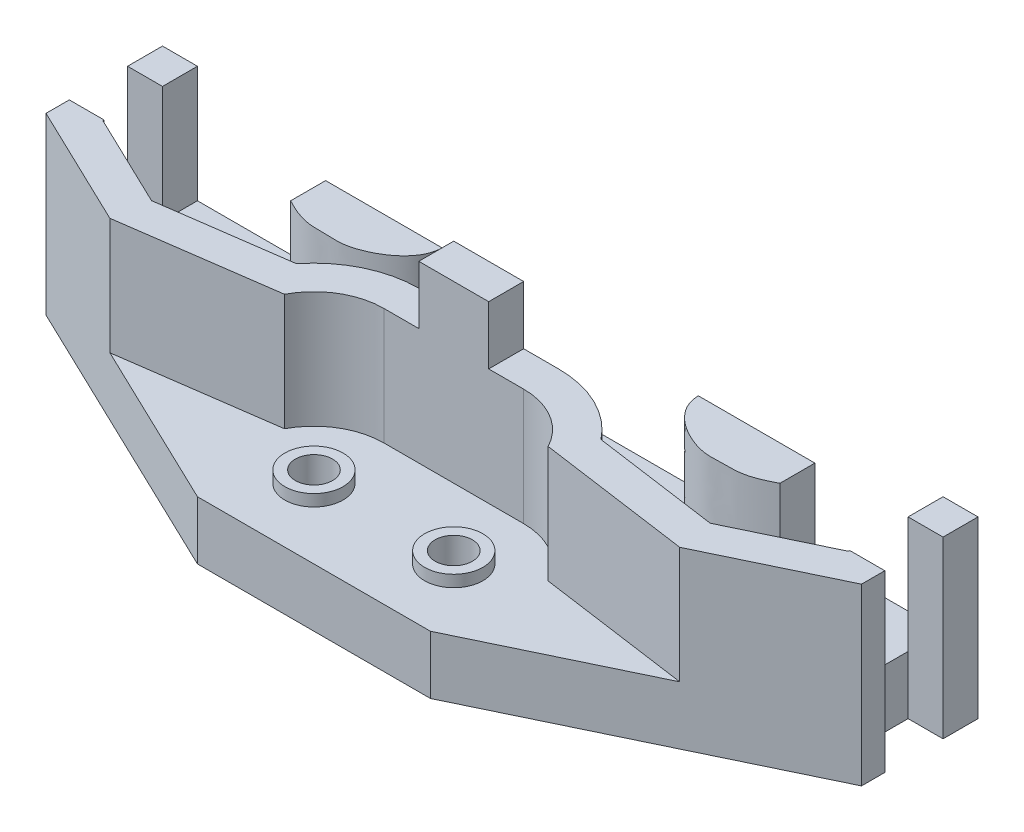
SolidWorks part; units mm, degrees
ref_plane "Front Plane" through (0, 0, 0) normal (0, 0, 1) x (1, 0, 0)
ref_plane "Top Plane" through (0, 0, 0) normal (0, 1, 0) x (1, 0, 0)
ref_plane "Right Plane" through (0, 0, 0) normal (1, 0, 0) x (0, 0, -1)
sketch "Sketch1" plane through (0, 0, 0) normal (0, 1, 0) x (1, 0, 0)
  line L0 (0, 0) -> (20, 0)
  line L1 (10, 0) -> (10, 12) construction
  line L2 (10, 12) -> (-25, 12) construction
  line L3 (0, 0) -> (-25, 12)
  line L4 (-25, 12) -> (-25, 22)
  line L5 (-25, 22) -> (45, 22)
  line L6 (45, 22) -> (45, 12)
  line L7 (45, 12) -> (20, 0)
  dimension "D1" = 35
  dimension "D2" = 20
  dimension "D3" = 12
  dimension "D4" = 70
  dimension "D5" = 10
  dimension "D6" = 10
extrude "Boss-Extrude1" add sketch "Sketch1" along normal blind 5
ref_plane "Plane1" through (10, 0, 0) normal (1, 0, 0) x (0, 0, -1)
sketch "Sketch2" plane through (0, 5, 0) normal (0, 1, 0) x (1, 0, 0)
  line L0 (10, 0) -> (10, 22) construction
  line L1 (0, 0) -> (20, 0) construction
  line L2 (45, 22) -> (-25, 22) construction
  circle A0 centre (4, 6) radius 1.6
  circle A1 centre (16, 6) radius 1.6
  dimension "D1" = 3.2
  dimension "D2" = 6
  dimension "D3" = 6
extrude "Cut-Extrude1" cut sketch "Sketch2" against normal blind 3
sketch "Sketch3" plane through (0, 5, 0) normal (0, 1, 0) x (1, 0, 0)
  line L0 (4, 6) -> (-8.7631, 4.2063) construction
  line L1 (-25, 12) -> (0, 0) construction
  line L2 (-8.7631, 4.2063) -> (-8.7631, 22) construction
  line L3 (45, 22) -> (-25, 22) construction
  line L4 (-2.3815, 5.1031) -> (-2.8686, 8.5691) construction
  line L5 (-2.8686, 8.5691) -> (4.0027, 9.5348) construction
  line L6 (-1.3131, 8.7877) -> (-14.4587, 6.9402)
  line L7 (10, 0) -> (10, 22) construction
  line L8 (0, 0) -> (20, 0) construction
  line L10 (-14.4587, 6.9402) -> (-25, 12)
  line L11 (-25, 12) -> (-25, 22)
  line L12 (-25, 22) -> (-22, 22)
  line L13 (-21.9703, 13.8734) -> (-25, 15.3277) construction
  line L14 (-21.9703, 13.8734) -> (-9.0961, 7.6939) construction
  line L15 (-19.7294, 9.4701) -> (-13.715, 22) construction
  line L17 (-3.069, 11.5704) -> (-13.9782, 10.0372)
  line L19 (-7.8859, 7.8639) -> (-9.8726, 22) construction
  line L21 (4, 12) -> (4, 15) construction
  line L30 (-22, 22) -> (-22, 13.8877)
  line L32 (0.4296, 9.0326) -> (0.012, 12.0034) construction
  line L33 (0.012, 12.0034) -> (-19.3407, 9.2836) construction
  line L34 (-22, 13.8877) -> (-13.9782, 10.0372)
  line L35 (4, 15) -> (16, 15)
  line L36 (4, 12) -> (16, 12)
  line L37 (21.3131, 8.7877) -> (34.4587, 6.9402)
  line L38 (34.4587, 6.9402) -> (45, 12)
  line L39 (45, 12) -> (45, 22)
  line L40 (45, 22) -> (42, 22)
  line L41 (42, 22) -> (42, 13.8877)
  line L42 (42, 13.8877) -> (33.9782, 10.0372)
  line L43 (23.069, 11.5704) -> (33.9782, 10.0372)
  arc A0 (-1.3131, 8.7877) -> (4, 12) centre (4, 6) cw
  arc A4 (4, 15) -> (-3.069, 11.5704) centre (4, 6) ccw
  arc A5 (21.3131, 8.7877) -> (16, 12) centre (16, 6) ccw
  arc A6 (16, 15) -> (23.069, 11.5704) centre (16, 6) cw
  point P34 (10, 12)
  point P35 (10, 12)
  point P36 (10, 15)
  point P52 (10, 15)
  dimension "D4" = 6
  dimension "D1" = 82
  dimension "D2" = 3.5
  dimension "D3" = 90
  dimension "D5" = 90
  dimension "D6" = 90
  dimension "D7" = 3
  dimension "D8" = 3
  dimension "D9" = 3
  dimension "D10" = 3
  dimension "D11" = 3
  dimension "D12" = 90
extrude "Boss-Extrude2" add sketch "Sketch3" along normal blind 10
sketch "Sketch9" plane through (0, 15, 0) normal (0, 1, 0) x (1, 0, 0)
  line L0 (10, 12) -> (10, 15) construction
  line L1 (4, 12) -> (16, 12) construction
  line L2 (16, 15) -> (4, 15) construction
  line L3 (16, 15) -> (4, 15) construction
  line L4 (7, 12) -> (13, 12)
  line L5 (7, 12) -> (7, 15)
  line L6 (7, 15) -> (13, 15)
  line L7 (13, 12) -> (13, 15)
  dimension "D1" = 3
  dimension "D2" = 3
extrude "Boss-Extrude3" add sketch "Sketch9" along normal blind 5
sketch "Sketch12" plane through (0, 15, 0) normal (0, 1, 0) x (1, 0, 0)
  line L0 (-25, 22) -> (-25, 12) construction
  line L1 (-25, 19) -> (-22, 19)
  line L2 (-25, 19) -> (-25, 14)
  line L3 (-25, 14) -> (-22, 14)
  line L4 (-22, 19) -> (-22, 14)
  line L5 (-22, 13.8877) -> (-22, 22) construction
  line L6 (-22, 22) -> (-25, 22) construction
  line L7 (10, 22) -> (10, 0) construction
  line L8 (42, 22) -> (-22, 22) construction
  line L9 (0, 0) -> (20, 0) construction
  line L10 (45, 14) -> (42, 14)
  line L11 (42, 19) -> (42, 14)
  line L12 (45, 19) -> (42, 19)
  line L13 (45, 19) -> (45, 14)
  dimension "D1" = 3
  dimension "D2" = 5
extrude "Cut-Extrude4" cut sketch "Sketch12" against normal blind 17
sketch "Sketch14" plane through (0, 5, 0) normal (0, 1, 0) x (1, 0, 0)
  line L0 (42, 22) -> (-22, 22) construction
  line L1 (21, 22) -> (31, 22)
  line L3 (26, 18) -> (28.2891, 18)
  line L4 (31, 22) -> (31, 19)
  line L5 (10, 22) -> (10, 0) construction
  line L6 (0, 0) -> (20, 0) construction
  line L7 (-0.7999, 18) -> (-10.7999, 18)
  line L8 (-11, 22) -> (-10.7999, 18)
  line L9 (-1, 22) -> (-11, 22)
  line L10 (-1, 22) -> (-0.7999, 18)
  line L13 (25.9305, 18) -> (23.1394, 18) construction
  line L14 (21, 19.713) -> (21, 24.3845) construction
  spline S0 degree 3 poles (21, 22) (21, 19.7457) (24.6092, 17.8685) (27.9309, 18.1418) (28.7395, 17.7851) (31, 19) knots 0 0 0 0 0.402282 0.502282 1 1 1 1
  point P2 (31.102, 19)
  point P15 (21.2001, 22)
  point P18 (0, 0)
  point P24 (26.0428, 18)
  line M17 (42, 22) -> (-22, 22)
  dimension "D1" = 4
  dimension "D2" = 10
  dimension "D3" = 3
  dimension "D4" = 21
  dimension "D5" = 5
extrude "Boss-Extrude5" add sketch "Sketch14" along normal offset from surface (7 mm away) 3 contours S0 L4 M17 region at (26.4101, 5, -20.2182) up to face at (28.8051, 15, -12.2313)
sketch "Sketch20" plane through (0, 5, 0) normal (0, 1, 0) x (1, 0, 0)
  line L0 (10, 0) -> (10, 12) construction
  line L1 (0, 0) -> (20, 0) construction
  line L2 (7, 12) -> (13, 12) construction
  circle A0 centre (4, 6) radius 2.5
  circle A1 centre (4, 6) radius 1.6
  circle A2 centre (16, 6) radius 2.5
  circle A3 centre (16, 6) radius 1.6
  dimension "D1" = 5
extrude "Boss-Extrude7" add sketch "Sketch20" along normal blind 1
sketch "Sketch21" plane through (0, 0, 0) normal (0, -1, 0) x (1, 0, 0)
  line L0 (45, -22) -> (-25, -22) construction
  line L1 (16, -22) -> (4, -22)
  line L2 (16, -22) -> (16, -12)
  line L3 (16, -12) -> (4, -12)
  line L4 (4, -22) -> (4, -12)
  point P9 (10, -22)
  point P10 (10, -22)
  dimension "D1" = 12
  dimension "D2" = 10
extrude "Boss-Extrude9" add sketch "Sketch21" along normal blind 8
sketch "Sketch25" plane through (16, 0, 0) normal (1, 0, 0) x (0, 0, -1)
  line L0 (22, -8) -> (12, -8) construction
  line L1 (10.942, 0) -> (13.332, 0) construction
  line L2 (14.7879, -8) -> (15.61, -8) construction
  line L3 (12, 0) -> (12, -8)
  line L4 (12, -8) -> (16, -8)
  spline S0 degree 3 poles (16, -8) (14.9953, -8) (14.7066, -3.7583) (13.3144, 0) (12, 0) knots 0 0 0 0 0.541617 1 1 1 1
  dimension "D1" = 6
extrude "Cut-Extrude12" cut sketch "Sketch25" against normal up to next
sketch "Sketch22" plane through (0, 0, -22) normal (0, 0, -1) x (-1, 0, 0)
  line L0 (-4, -8) -> (-16, -8) construction
  circle A0 centre (-10, -2) radius 2.575
  point P5 (-10, -8)
  dimension "D1" = 5.15
  dimension "D2" = 6
extrude "Cut-Extrude9" cut sketch "Sketch22" against normal up to vertex (10 mm away) up to point (4, 0, -12)
sketch "Sketch23" plane through (0, 0, -22) normal (0, 0, -1) x (-1, 0, 0)
  circle A0 centre (-10, -2) radius 4.05
  dimension "D1" = 8.1
extrude "Cut-Extrude10" cut sketch "Sketch23" against normal blind 2
sketch "Sketch24" plane through (0, 0, -22) normal (0, 0, -1) x (-1, 0, 0)
  line L0 (-4, -8) -> (-4, 0) construction
  line L1 (-4, -8) -> (-16, -8) construction
  line L2 (-16, -8) -> (-16, 0) construction
  line L3 (-4, -8) -> (-4, -2)
  line L4 (-4, -8) -> (-16, -8)
  line L5 (-16, -8) -> (-16, -2)
  arc A0 (-16, -2) -> (-4, -2) centre (-10, -2) ccw
  line M10 (-16, 0) -> (-16, -8)
  line M11 (-16, -8) -> (-4, -8)
  line M12 (-4, -8) -> (-4, 0)
extrude "Cut-Extrude11" cut sketch "Sketch24" against normal up to next contours A0 M10 M11 | A0 L4 M12 region at (5.3402, -6.6598, -22) region at (14.6598, -6.6598, -22)
sketch "Sketch26" plane through (0, 0, -22) normal (0, 0, -1) x (-1, 0, 0)
  line L0 (-45, 0) -> (-16, 0) construction
  line L1 (-31, 0) -> (-21, 0)
  line L2 (-31, 0) -> (-31, -5)
  line L3 (-31, -5) -> (-21, -5)
  line L4 (-21, 0) -> (-21, -5)
  line L7 (-45, 15) -> (-45, 0) construction
  point P6 (-26, 0)
  dimension "D1" = 19
  dimension "D2" = 10
  dimension "D3" = 5
extrude "Boss-Extrude10" add sketch "Sketch26" against normal blind 10
sketch "Sketch29" plane through (31, 0, 0) normal (1, 0, 0) x (0, 0, -1)
  line L0 (12, -5) -> (22, -5) construction
  line L1 (13.5409, -5) -> (15.5485, -5) construction
  line L2 (10.4353, 0) -> (13.6364, 0) construction
  line L3 (22, 0) -> (22, -5) construction
  line L4 (12, 0) -> (12, -5) construction
  line L5 (12, -5) -> (14, -5)
  line L6 (12, 0) -> (12, -5)
  spline S0 degree 3 poles (14, -5) (13.4037, -5) (12.9336, -2.6301) (12.7861, 0) (12, 0) knots 0 0 0 0 0.556921 1 1 1 1
  point P2 (0, 0)
  point P4 (0, 0)
  point P14 (13.1999, -2.0846)
  point P15 (12.9801, -2.2796)
  dimension "D1" = 8
extrude "Cut-Extrude15" cut sketch "Sketch29" against normal up to next
sketch "Sketch27" plane through (0, 0, -22) normal (0, 0, -1) x (-1, 0, 0)
  line L0 (-31, -5) -> (-21, -5) construction
  line L2 (-21, 12) -> (-21, 5) construction
  circle A0 centre (-26, 0.5) radius 2.1
  point P2 (0, 0)
  point P5 (-26, -5)
  point P8 (-21, 8.5)
  dimension "D1" = 4.2
  dimension "D2" = 8
extrude "Cut-Extrude13" cut sketch "Sketch27" against normal blind 5
sketch "Sketch28" plane through (0, 0, -22) normal (0, 0, -1) x (-1, 0, 0)
  line L0 (-21, -5) -> (-21, 0) construction
  line L1 (-31, -5) -> (-21, -5) construction
  line L2 (-31, 0) -> (-31, -5) construction
  line L3 (-21, -5) -> (-21, 0)
  line L4 (-31, -5) -> (-21, -5)
  line L5 (-31, 0) -> (-31, -5)
  arc A0 (-31, 0) -> (-21, 0) centre (-26, 0.5) ccw
  line M19 (-31, 0) -> (-31, -5)
  line M20 (-31, -5) -> (-21, -5)
  line M21 (-21, -5) -> (-21, 0)
extrude "Cut-Extrude14" cut sketch "Sketch28" against normal up to next contours A0 L4 M21 | A0 M19 M20 region at (26, -4.8882, -22)
mirror "Mirror1" about plane through (10, 0, 0) normal (1, 0, 0) of "Cut-Extrude14", "Cut-Extrude13", "Cut-Extrude15", "Boss-Extrude10"
mirror "Mirror2" about plane through (10, 0, 0) normal (1, 0, 0) of "Boss-Extrude5"
